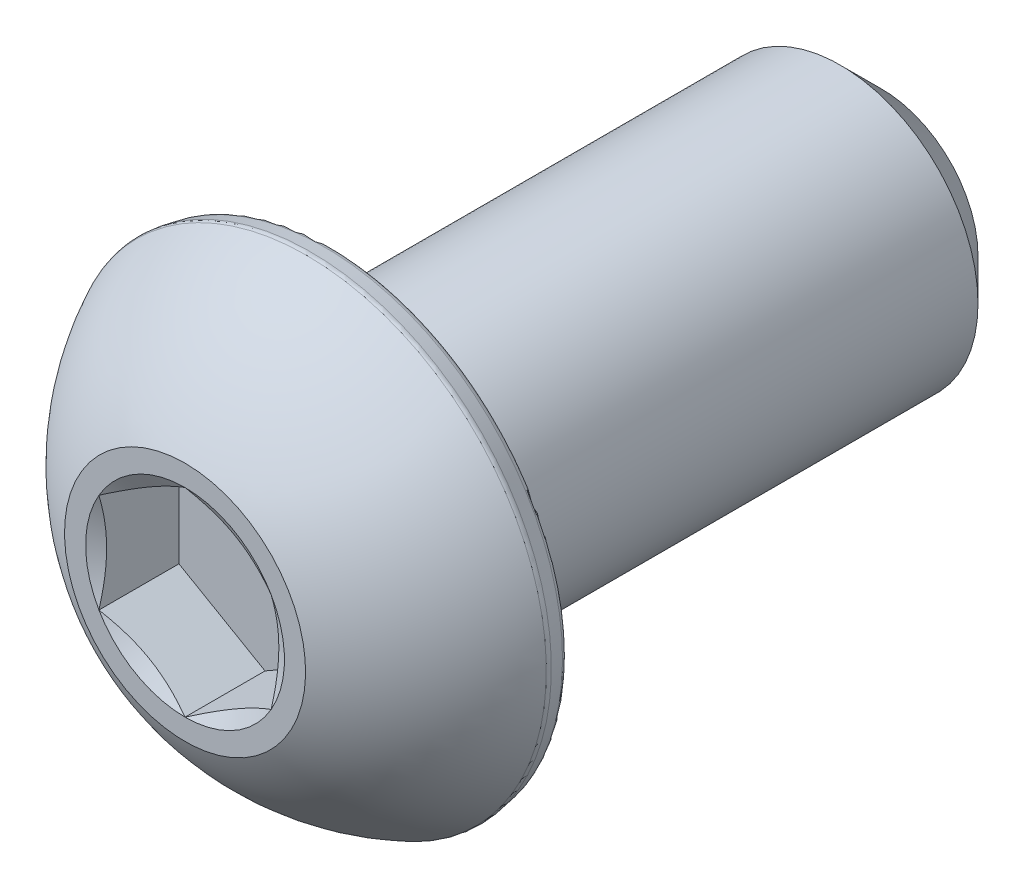
SolidWorks part; units mm, degrees
material "Plain Carbon Steel"
ref_plane "Front Plane" through (0, 0, 0) normal (0, 0, 1) x (1, 0, 0)
ref_plane "Top Plane" through (0, 0, 0) normal (0, 1, 0) x (1, 0, 0)
ref_plane "Right Plane" through (0, 0, 0) normal (1, 0, 0) x (0, 0, -1)
sketch "Sketch1" plane through (0, 0, 0) normal (1, 0, 0) x (0, 0, -1)
  line L0 (-8.0264, 0) -> (8.0264, 0) construction
  line L1 (-8.0264, 0) -> (-8.0264, 5.5499)
  line L2 (-8.0264, 5.5499) -> (-4.6736, 5.5499)
  line L3 (-4.6736, 5.5499) -> (-4.6736, 3.175)
  line L4 (-4.6736, 3.175) -> (8.0264, 3.175)
  line L5 (8.0264, 3.175) -> (8.0264, 0)
  point P2 (0, 0)
  point P4 (6.7564, 0)
  point P9 (6.1214, 3.175)
  point P10 (6.1214, -3.175)
  point P11 (8.0264, -3.175)
  point P15 (-6.1824, 0)
  dimension "Head Height" = 3.3528
  dimension "Head Diameter" = 11.0998
  dimension "Length" = 12.7
  dimension "Screw Size Decimal Equivalent" = 6.35
  dimension "Thread Pitch" = 1.27
  dimension "D1" = 1.905
  dimension "D2" = 1.844
sketch "Sketch2" plane through (0, 0, 0) normal (0, 0, 1) x (1, 0, 0)
  line L0 (0, 3.175) -> (0, 0) construction
  line L1 (0, 2.2914) -> (-1.9844, 1.1457)
  line L2 (-1.9844, 1.1457) -> (-1.9844, -1.1457)
  line L3 (-1.9844, -1.1457) -> (0, -2.2914)
  line L4 (0, -2.2914) -> (1.9844, -1.1457)
  line L5 (1.9844, -1.1457) -> (1.9844, 1.1457)
  line L6 (1.9844, 1.1457) -> (0, 2.2914)
  circle A0 centre (0, 0) radius 1.9844 construction
  circle A1 centre (0, 0) radius 2.7781
  point P10 (0, 2.7781)
  dimension "D1" = 5.5563
  dimension "Drive Size" = 3.9688
sketch "Sketch3" plane through (0, 0, 0) normal (1, 0, 0) x (0, 0, -1)
  line L0 (-8.0264, 0) -> (-8.0264, 2.7781)
  line L1 (-8.0264, 0) -> (-8.0264, 5.5499) construction
  line L2 (-8.0264, 5.5499) -> (-4.6736, 5.5499) construction
  line L3 (-5.1765, 5.5499) -> (-4.6736, 5.4612)
  line L4 (-4.6736, 5.5499) -> (-4.6736, 3.175) construction
  line L5 (-4.6736, 5.4612) -> (-4.6736, 3.175)
  line L6 (-8.0264, 0) -> (8.0264, 0) construction
  line L7 (-8.0264, 0) -> (8.0264, 0)
  line L8 (8.0264, 0) -> (8.0264, 2.2225)
  line L9 (8.0264, 3.175) -> (8.0264, 0) construction
  line L10 (8.0264, 2.2225) -> (7.0739, 3.175)
  line L11 (-4.6736, 3.175) -> (8.0264, 3.175) construction
  line L12 (7.0739, 3.175) -> (-4.6736, 3.175)
  arc A0 (-8.0264, 2.7781) -> (-5.1765, 5.5499) centre (-2.5516, 0) cw
  dimension "D1" = 0.5029
  dimension "D2" = 10
  dimension "D3" = 45
  dimension "D4" = 0.9525
revolve "Revolve1" add sketch "Sketch3" angle 360 about L7
sketch "Sketch4" plane through (0, 0, 8.0264) normal (0, 0, 1) x (1, 0, 0)
  line L0 (-1.9844, -1.1457) -> (0, -2.2914) construction
  line L1 (-1.9844, 1.1457) -> (-1.9844, -1.1457) construction
  line L2 (0, 2.2914) -> (-1.9844, 1.1457) construction
  line L3 (1.9844, 1.1457) -> (0, 2.2914) construction
  line L4 (1.9844, -1.1457) -> (1.9844, 1.1457) construction
  line L5 (0, -2.2914) -> (1.9844, -1.1457) construction
  line L6 (-1.9844, -1.1457) -> (0, -2.2914)
  line L7 (-1.9844, 1.1457) -> (-1.9844, -1.1457)
  line L8 (0, 2.2914) -> (-1.9844, 1.1457)
  line L9 (1.9844, 1.1457) -> (0, 2.2914)
  line L10 (1.9844, -1.1457) -> (1.9844, 1.1457)
  line L11 (0, -2.2914) -> (1.9844, -1.1457)
extrude "Cut-Extrude1" cut sketch "Sketch4" against normal up to vertex (1.844 mm away) up to point (0, 0, 6.1824)
sketch "Sketch5" plane through (0, 0, 8.0264) normal (0, 0, 1) x (1, 0, 0)
  circle A0 centre (0, 0) radius 2.2914
extrude "Cut-Extrude2" cut sketch "Sketch5" against normal up to vertex (1.844 mm away) draft 60 up to point (0, 0, 6.1824)
fillet "Fillet1" radius 0.1676 2 edges at (5.5499, 0, 5.1765) (5.4612, 0, 4.6736)
split "Split1" [suppressed] bodies to split 106
sketch "Sketch6" [suppressed] plane through (0, 0, -8.0264) normal (0, 0, -1) x (-1, 0, 0)
  circle A0 centre (0, 0) radius 3.175 construction
  circle A1 centre (0, 0) radius 3.175
curve "Helix/Spiral1" [suppressed] pitch 1.27 height 13.97 turns 11
sketch "Sketch7" [suppressed] plane through (0, 0, 0) normal (1, 0, 0) x (0, 0, -1)
  line L0 (7.947, 3.3125) -> (8.582, 2.2126) construction
  line L1 (8.582, 2.2126) -> (9.217, 3.3125) construction
  line L2 (9.217, 3.3125) -> (7.947, 3.3125) construction
  line L3 (7.9867, 3.2437) -> (9.1773, 3.2437)
  line L4 (9.1773, 3.2437) -> (8.6614, 2.3501)
  line L5 (8.6614, 2.3501) -> (8.5027, 2.3501)
  line L6 (8.5027, 2.3501) -> (7.9867, 3.2437)
  line L7 (8.582, 2.3501) -> (8.582, 2.2126) construction
  line L8 (8.0264, 3.175) -> (9.1377, 3.175) construction
  line L9 (8.582, 3.3125) -> (8.582, 3.175) construction
  point P12 (8.582, 3.2437)
  dimension "D1" = 1.27
  dimension "D2" = 0.1588
sweep "Cut-Sweep1" [suppressed] cut profiles "Sketch7" path "Helix/Spiral1"
sketch "Sketch8" [suppressed] plane through (0, 0, 4.6736) normal (0, 0, -1) x (-1, 0, 0)
  circle A0 centre (0, 0) radius 3.3125
extrude "Boss-Extrude1" [suppressed] add sketch "Sketch8" along normal up to vertex draft 45
equation "\"D1@Sketch1\"=\"Thread Pitch@Sketch1\"*1.5"
equation "\"D2@Sketch1\"=0.55*\"Head Height@Sketch1\""
equation "\"D1@Sketch2\"=\"Drive Size@Sketch2\"*1.4"
equation "\"D1@Sketch3\"=0.15*\"Head Height@Sketch1\""
equation "\"D4@Sketch3\"=0.75*\"Thread Pitch@Sketch1\""
equation "\"D1@Fillet1\"=.05*\"Head Height@Sketch1\""
equation "\"D4@Helix/Spiral1\"=\"Thread Pitch@Sketch1\""
equation "\"D3@Helix/Spiral1\"=\"Length@Sketch1\"+\"Thread Pitch@Sketch1\""
equation "\"D2@Sketch7\"=\"D1@Sketch7\"/8"
equation "\"D1@Sketch7\"=\"Thread Pitch@Sketch1\""
